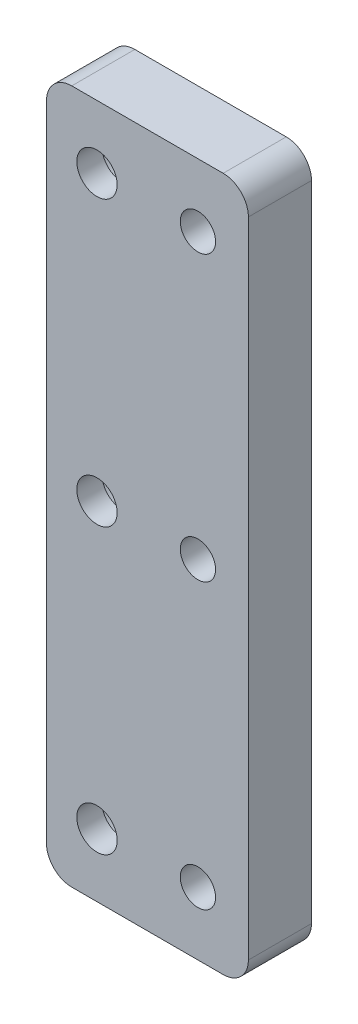
SolidWorks part; units mm, degrees
ref_plane "Front Plane" through (0, 0, 0) normal (0, 0, 1) x (1, 0, 0)
ref_plane "Top Plane" through (0, 0, 0) normal (0, 1, 0) x (1, 0, 0)
ref_plane "Right Plane" through (0, 0, 0) normal (1, 0, 0) x (0, 0, -1)
sketch "Sketch1" plane through (0, 0, 0) normal (0, 0, 1) x (1, 0, 0)
  line L1 (-4, -27.5) -> (4, -27.5)
  line L2 (-4, -27.5) -> (-4, 27.5)
  line L3 (-4, 27.5) -> (4, 27.5)
  line L4 (4, -27.5) -> (4, 27.5)
  line L5 (-4, -27.5) -> (4, 27.5) construction
  line L6 (-4, 27.5) -> (4, -27.5) construction
  point P0 (0, 0)
  dimension "D1" = 8
  dimension "D2" = 55
extrude "Boss-Extrude1" add sketch "Sketch1" along normal blind 2.5 and the other way blind 2.5
sketch "Sketch2" plane through (0, 0, 2.5) normal (0, 0, 1) x (1, 0, 0)
  line L0 (0, 22.5) -> (0, -22.5) construction
  line L1 (0, -22.5) -> (0, -27.5) construction
  line L2 (-4, -27.5) -> (4, -27.5) construction
  line L3 (0, 22.5) -> (0, 27.5) construction
  line L4 (4, 27.5) -> (-4, 27.5) construction
  circle A0 centre (0, 22.5) radius 1.6
  circle A1 centre (0, -22.5) radius 1.6
  circle A2 centre (0, 0) radius 1.6
  dimension "D2" = 3.2
  dimension "D1" = 45
extrude "Cut-Extrude1" cut sketch "Sketch2" against normal through all
sketch "Sketch3" plane through (0, 0, 2.5) normal (0, 0, 1) x (1, 0, 0)
  line L0 (-4, -27.5) -> (4, -27.5) construction
  line L1 (4, 27.5) -> (12, 27.5)
  line L2 (4, 27.5) -> (4, -27.5)
  line L3 (4, -27.5) -> (12, -27.5)
  line L4 (12, 27.5) -> (12, -27.5)
  line L5 (0, 22.5) -> (8, 22.5) construction
  line L6 (8, 22.5) -> (8, 27.5) construction
  line L7 (8, 22.5) -> (8, -27.5) construction
  line L8 (0, 0) -> (8, 0) construction
  line L9 (0, -22.5) -> (8, -22.5) construction
  circle A0 centre (0, 22.5) radius 3.25 construction
  circle A1 centre (8, 22.5) radius 1.4
  circle A2 centre (8, 0) radius 1.4
  circle A3 centre (8, -22.5) radius 1.4
  point P22 (9.2364, 0)
  dimension "D2" = 6.5
  dimension "D3" = 2.8
  dimension "D1" = 8
extrude "Boss-Extrude3" add sketch "Sketch3" against normal through all
hole_wizard "CBORE for M5 Hex Head Bolt3" positions "3DSketch4" profile "Sketch8" counterbore size "M5" standard "ANSI Metric" end condition through all
sketch3d "3DSketch4"
  line L0 (0, 22.5, -2.5) -> (0, 22.5, 2.5) construction
  line L1 (0, -22.5, -2.5) -> (0, -22.5, 2.5) construction
  line L2 (0, 0, -2.5) -> (0, 0, 2.5) construction
  point P0 (0, 22.5, -2.5)
  point P4 (0, 0, 0)
  point P7 (0, -22.5, -2.5)
  point P11 (0, 0, -2.5)
sketch "Sketch8" plane through (0, 22.5, -2.5) normal (1, 0, 0) x (0, 1, 0)
  line L0 (0, 0) -> (0, 5)
  line L1 (0, 5) -> (1.6, 5)
  line L3 (1.6, 5) -> (1.6, 3)
  line L4 (1.6, 3) -> (3.5, 3)
  line L5 (3.5, 3) -> (3.5, 0)
  line L7 (3.5, 0) -> (0, 0)
  line L11 (0, -6.35) -> (0, 107.95) construction
  dimension "Thru Hole Dia." = 3.2
  dimension "Thru Hole Depth" = 5
  dimension "C'Bore Dia." = 7
  dimension "C'Bore Depth" = 3
fillet "Fillet1" radius 2 4 edges at (-4, -27.5, 0) (12, -27.5, 0) (-4, 27.5, 0) (12, 27.5, 0)
